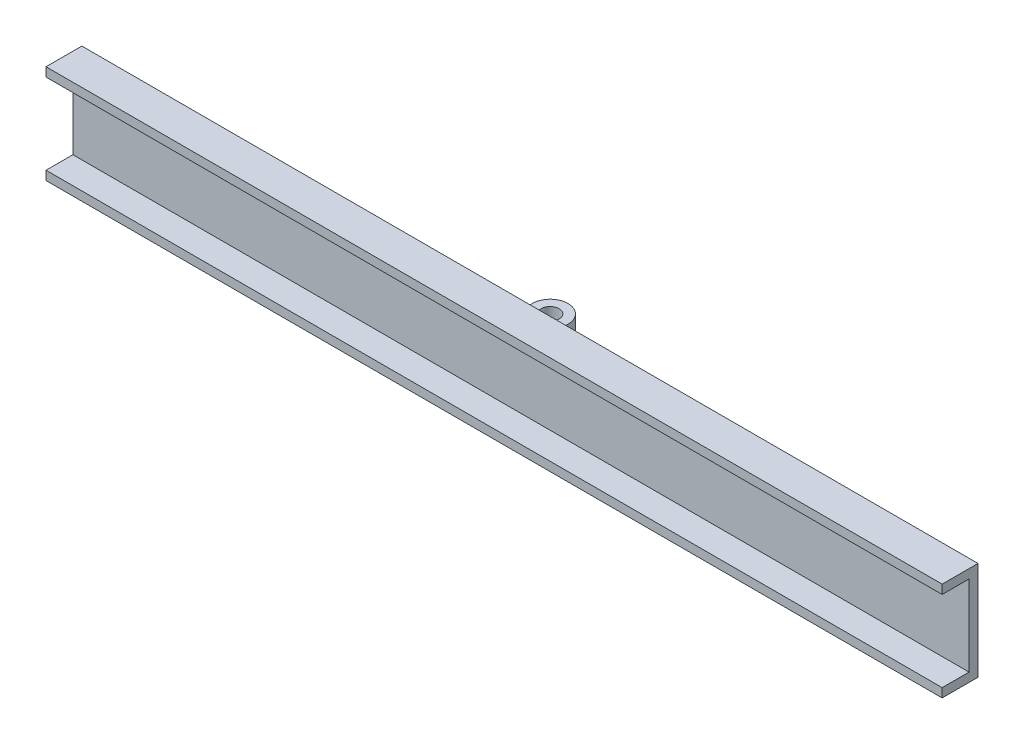
SolidWorks part; units mm, degrees
material "PLA"
ref_plane "Front Plane" through (0, 0, 0) normal (1, 0, 0) x (0, 1, 0)
ref_plane "Top Plane" through (0, 0, 0) normal (0, 0, 1) x (0, 1, 0)
ref_plane "Right Plane" through (0, 0, 0) normal (0, 1, 0) x (-1, 0, 0)
sketch "Sketch1" plane through (0, 0, 0) normal (1, 0, 0) x (0, 1, 0)
  line L16 (0, 7.5) -> (-2.5, 7.5)
  line L17 (0, 0) -> (22.5, 0)
  line L18 (0, 0) -> (0, 7.5)
  line L19 (0, 7.5) -> (22.5, 7.5) construction
  line L20 (22.5, 0) -> (22.5, 7.5)
  line L21 (-2.5, 7.5) -> (-2.5, -2.5)
  line L22 (-2.5, -2.5) -> (25, -2.5)
  line L23 (25, -2.5) -> (25, 7.5)
  line L24 (22.5, 7.5) -> (25, 7.5)
  dimension "D1" = 7.5
  dimension "D2" = 22.5
  dimension "D3" = 2.5
  dimension "D4" = 2.5
extrude "Boss-Extrude1" add sketch "Sketch1" along normal blind 250
sketch "Sketch3" plane through (0, -2.5, 0) normal (0, -1, 0) x (1, 0, 0)
  line L0 (120.0194, -2.5) -> (129.9806, -2.5)
  line L1 (250, -2.5) -> (0, -2.5) construction
  line L2 (129.9806, -2.5) -> (129.9806, -7.5)
  line L3 (120.0194, -2.5) -> (120.0194, -8.1217)
  line L4 (0, 7.5) -> (0, -2.5) construction
  arc A0 (120.0194, -8.1217) -> (129.9806, -7.5) centre (125.0194, -8.1217) ccw
  circle A1 centre (125.0194, -8.1217) radius 2.5
  point P5 (125, -2.5)
  dimension "D2" = 5
  dimension "D3" = 5
  dimension "D4" = 125
extrude "Boss-Extrude2" add sketch "Sketch3" against normal up to surface (27.5 mm away) up to face at (125, 25, 2.5)
sketch "Sketch6" plane through (0, -2.5, 0) normal (0, -1, 0) x (1, 0, 0)
  line L0 (120.0194, -2.5) -> (0, -2.5) construction
  line L1 (117.5385, -2.5) -> (131.3691, -2.5)
  line L2 (117.5385, -2.5) -> (117.5385, -13.6365)
  line L3 (117.5385, -13.6365) -> (131.3691, -13.6365)
  line L4 (131.3691, -2.5) -> (131.3691, -13.6365)
extrude "Cut-Extrude2" cut sketch "Sketch6" against normal blind 5
sketch "Sketch7" plane through (0, 25, 0) normal (0, 1, 0) x (-1, 0, 0)
  line L0 (-250, -2.5) -> (-129.9806, -2.5) construction
  line L1 (-136.5723, -2.5) -> (-116.3235, -2.5)
  line L2 (-136.5723, -2.5) -> (-136.5723, -14.7915)
  line L3 (-136.5723, -14.7915) -> (-116.3235, -14.7915)
  line L4 (-116.3235, -2.5) -> (-116.3235, -14.7915)
extrude "Cut-Extrude3" cut sketch "Sketch7" against normal blind 5
equation "\"D1@Sketch1\"=\"ball_diameter\" * 0.25"
equation "\"D2@Sketch1\"=\"ball_diameter\" * 0.75"
equation "\"D3@Sketch1\"=\"wall_thickness\""
equation "\"D4@Sketch1\"=\"wall_thickness\""
equation "\"D1@Boss-Extrude1\"=\"track_length\""
equation "\"D2@Sketch3\"= \"axle\""
equation "\"ball_diameter\"= 3cm"
equation "\"wall_thickness\" = 0.25cm"
equation "\"track_length\" = 25cm"
equation "\"axle\" = 5mm"
equation "\"D3@Sketch3\"=\"axle\" * 1"
equation "\"D4@Sketch3\"=\"track_length\" / 2"
equation "\"pillar_width\" = 2.75cm"
